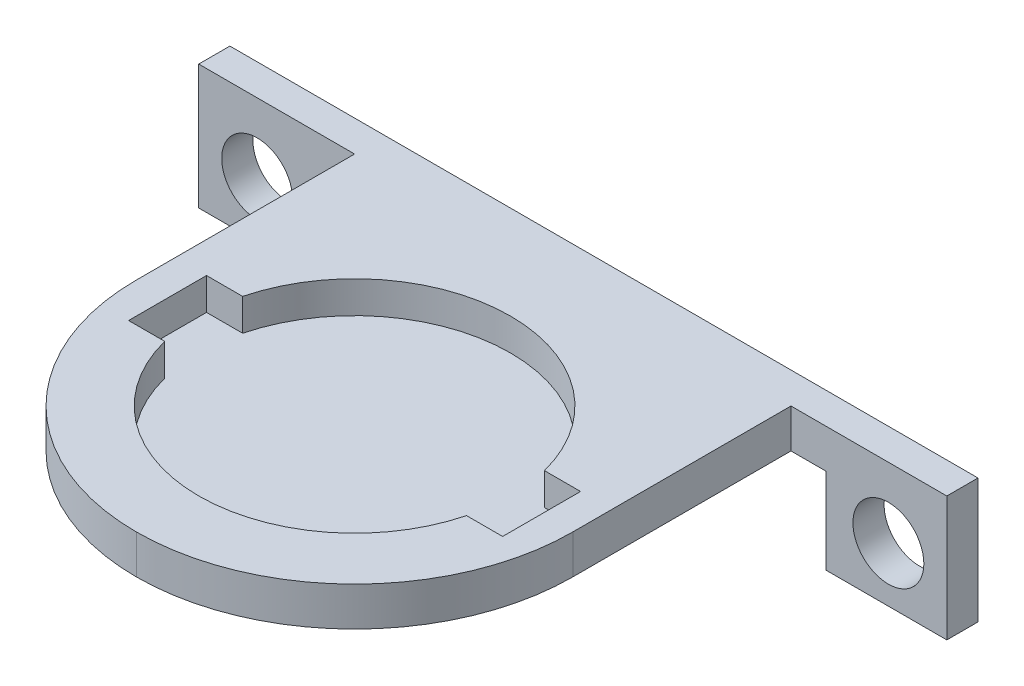
SolidWorks part; units mm, degrees
material "사용자정의 플라스틱"
ref_plane "정면" through (0, 0, 0) normal (0, 0, 1) x (1, 0, 0)
ref_plane "윗면" through (0, 0, 0) normal (0, 1, 0) x (1, 0, 0)
ref_plane "우측면" through (0, 0, 0) normal (1, 0, 0) x (0, 0, -1)
sketch "스케치1" plane through (0, 0, 0) normal (0, 0, 1) x (1, 0, 0)
  line L1 (-48, 8) -> (48, 8)
  line L2 (-48, 8) -> (-48, -8)
  line L3 (-48, -8) -> (48, -8)
  line L4 (48, 8) -> (48, -8)
  line L5 (-48, 8) -> (48, -8) construction
  line L6 (-48, -8) -> (48, 8) construction
  point P0 (0, 0)
  dimension "D1" = 96
  dimension "D2" = 16
extrude "보스-돌출1" add sketch "스케치1" along normal blind 4
sketch "스케치2" plane through (0, 0, 4) normal (0, 0, 1) x (1, 0, 0)
  line L0 (48, 8) -> (-48, 8) construction
  line L1 (-28, 8) -> (28, 8)
  line L2 (-28, 8) -> (-28, 3)
  line L3 (-28, 3) -> (28, 3)
  line L4 (28, 8) -> (28, 3)
  point P6 (-13.9943, 11.0121)
  point P7 (-17.3146, 0)
  point P8 (18.5699, 0.7958)
  dimension "D1" = 5
  dimension "D2" = 56
  dimension "D3" = 28
extrude "보스-돌출2" add sketch "스케치2" along normal blind 56
sketch "스케치3" plane through (0, 0, 4) normal (0, 0, 1) x (1, 0, 0)
  line L0 (-48, -8) -> (48, -8) construction
  line L1 (-32.5, -8) -> (32.5, -8)
  line L2 (-32.5, -8) -> (-32.5, 3)
  line L3 (-32.5, 3) -> (32.5, 3)
  line L4 (32.5, -8) -> (32.5, 3)
  line L5 (-48, 8) -> (-48, -8) construction
  line L6 (48, -8) -> (48, 8) construction
  line L7 (-28, 3) -> (28, 3) construction
  dimension "D1" = 15.5
  dimension "D2" = 15.5
  dimension "D3" = 0
extrude "컷-돌출1" cut sketch "스케치3" against normal blind 50
sketch "스케치4" plane through (0, 0, 4) normal (0, 0, 1) x (1, 0, 0)
  line L0 (-48, 8) -> (-48, -8) construction
  line L1 (48, -8) -> (48, 8) construction
  line L2 (-48, -8) -> (-32.5, -8) construction
  line L3 (32.5, -8) -> (48, -8) construction
  circle A0 centre (40.5, -1) radius 4.55
  circle A1 centre (-40.5, -1) radius 4.55
  dimension "D1" = 9.1
  dimension "D2" = 9.1
  dimension "D3" = 7.5
  dimension "D4" = 7.5
  dimension "D5" = 7
  dimension "D6" = 7
extrude "컷-돌출2" cut sketch "스케치4" against normal through all
fillet "필렛1" radius 28 2 edges at (-28, 5.5, 60) (28, 5.5, 60)
sketch "스케치5" plane through (0, 8, 0) normal (0, 1, 0) x (1, 0, 0)
  line L1 (-16, -27) -> (-24, -27)
  line L2 (-16, -27) -> (-16, -37)
  line L3 (-16, -37) -> (-24, -37)
  line L4 (-24, -27) -> (-24, -37)
  line L5 (-16, -27) -> (-24, -37) construction
  line L6 (-16, -37) -> (-24, -27) construction
  line L7 (16, -27) -> (24, -27)
  line L8 (16, -27) -> (16, -37)
  line L9 (16, -37) -> (24, -37)
  line L10 (24, -27) -> (24, -37)
  line L11 (16, -27) -> (24, -37) construction
  line L12 (16, -37) -> (24, -27) construction
  circle A0 centre (0, -32) radius 20
  point P2 (-20, -32)
  point P7 (20, -32)
  point P12 (0, 0)
  point P13 (0, 0)
  point P15 (0, 0)
  dimension "D1" = 40
  dimension "D2" = 10
  dimension "D3" = 8
  dimension "D4" = 8
  dimension "D5" = 10
extrude "컷-돌출3" cut sketch "스케치5" against normal blind 4.1 contours L7 A0 L1 L2 L3 L9 L8 | L9 A0 L7 L8 | A0 L9 L10 L7 | L1 A0 L3 L2 | A0 L1 L4 L3 region at (-17.8995, 8, 32) region at (0, 8, 32) region at (-21.8906, 8, 32) region at (17.8995, 8, 32) region at (21.8906, 8, 32)
